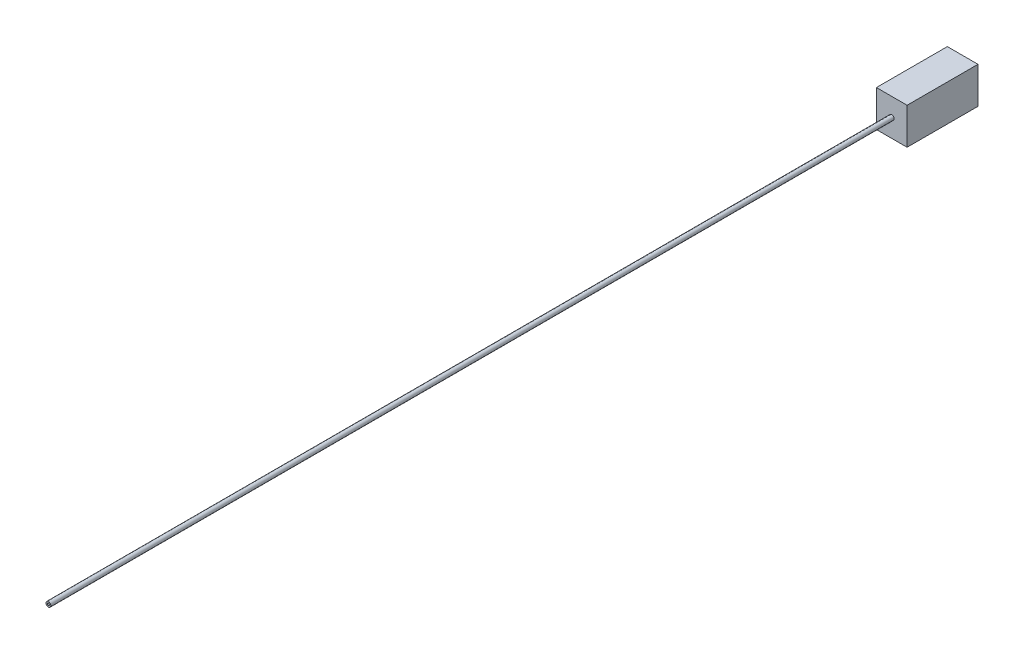
SolidWorks part; units mm, degrees
ref_plane "Plano frontal" through (0, 0, 0) normal (0, 0, 1) x (1, 0, 0)
ref_plane "Plano superior" through (0, 0, 0) normal (0, 1, 0) x (1, 0, 0)
ref_plane "Plano direito" through (0, 0, 0) normal (1, 0, 0) x (0, 0, -1)
sketch "Esboço1" plane through (0, 0, 0) normal (0, 0, 1) x (1, 0, 0)
  line L1 (4, -4.75) -> (-4, -4.75)
  line L2 (4, -4.75) -> (4, 4.75)
  line L3 (4, 4.75) -> (-4, 4.75)
  line L4 (-4, -4.75) -> (-4, 4.75)
  line L5 (4, -4.75) -> (-4, 4.75) construction
  line L6 (4, 4.75) -> (-4, -4.75) construction
  point P0 (0, 0)
  dimension "D1" = 9.5
  dimension "D2" = 8
extrude "Ressalto-extrusão1" add sketch "Esboço1" along normal blind 18.5
sketch "Esboço2" plane through (0, 0, 18.5) normal (0, 0, 1) x (1, 0, 0)
  circle A0 centre (0, 0) radius 0.625
  circle A1 centre (0, 0) radius 0.25
  dimension "D1" = 1.25
  dimension "D2" = 0.5
extrude "Ressalto-extrusão2" add sketch "Esboço2" along normal blind 220
extrude "Corte-extrusão1" cut sketch "Esboço2<3>" against normal blind 230 contours A1 region at (0, 0, 18.5)
sketch "Esboço2<3>" plane through (0, 0, 18.5) normal (0, 0, 1) x (1, 0, 0) same geometry as "Esboço2"
